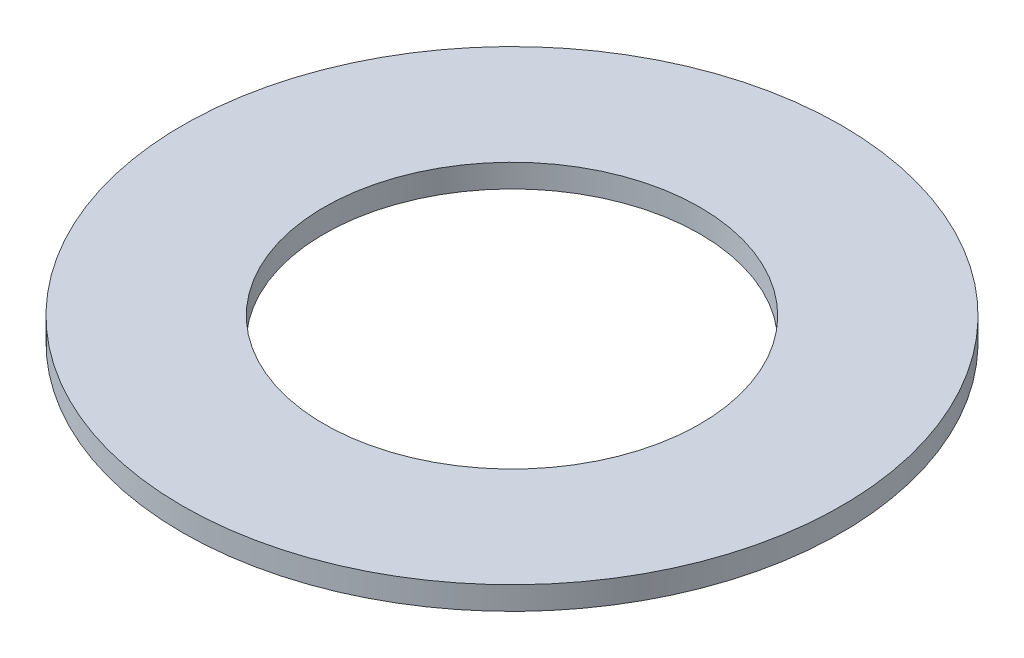
SolidWorks part; units mm, degrees
material "Polyetheretherketone (PEEK)"
ref_plane "Front Plane" through (0, 0, 0) normal (0, 0, 1) x (1, 0, 0)
ref_plane "Top Plane" through (0, 0, 0) normal (0, 1, 0) x (1, 0, 0)
ref_plane "Right Plane" through (0, 0, 0) normal (1, 0, 0) x (0, 0, -1)
sketch "Sketch1" plane through (0, 0, 0) normal (0, 0, 1) x (1, 0, 0)
  line L0 (0, 0) -> (0, 50000) construction
  line L2 (32.5, 2) -> (57, 2)
  line L3 (32.5, 2) -> (32.5, -2)
  line L4 (32.5, -2) -> (57, -2)
  line L5 (57, 2) -> (57, -2)
  point P7 (57, 0)
  dimension "D1" = 114
  dimension "D2" = 65
  dimension "D3" = 4
revolve "Revolve1" add sketch "Sketch1" angle 360 about L0
equation "\"CanSat_Len\"= 400mm"
equation "\"CanSat_Dia\"= 150mm"
equation "\"BodyTube_ID\"= 114mm"
equation "\"BodyTube_OD\"= 120mm"
equation "\"PayLoadBay_ID\"= 164mm"
equation "\"PayLoadBay_OD\"= 170mm"
equation "\"ParachuteBay_Pitch\"= 300mm"
equation "\"ElectronicsTray_PitchDist\"= 50mm"
equation "\"ElectronicsTray_Height\"= 140mm"
equation "\"MotorDia\"= 98mm"
equation "\"MotorLen\"= 289mm"
equation "\"D1@Sketch1\"=\"BodyTube_ID\""
